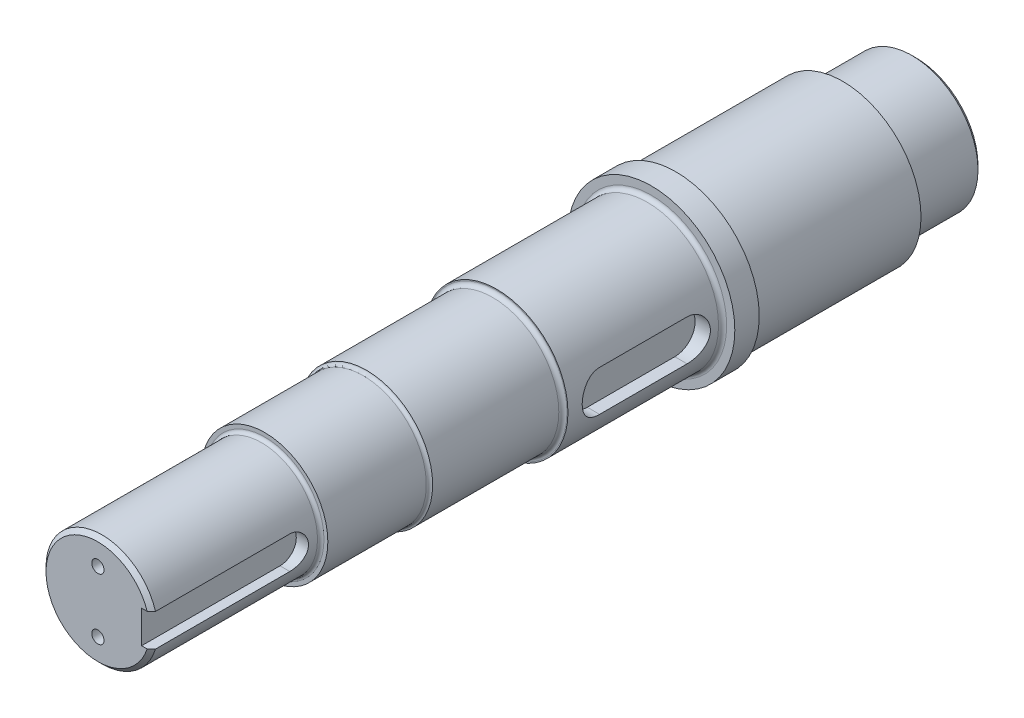
SolidWorks part; units mm, degrees
ref_plane "前视基准面" through (0, 0, 0) normal (0, 0, 1) x (1, 0, 0)
ref_plane "上视基准面" through (0, 0, 0) normal (0, 1, 0) x (1, 0, 0)
ref_plane "右视基准面" through (0, 0, 0) normal (1, 0, 0) x (0, 0, -1)
sketch "草图1" plane through (0, 0, 0) normal (0, 0, 1) x (1, 0, 0)
  circle A0 centre (0, 0) radius 32.5
  dimension "D1" = 65
extrude "凸台-拉伸1" add sketch "草图1" along normal blind 36
sketch "草图2" plane through (0, 0, 36) normal (0, 0, 1) x (1, 0, 0)
  circle A0 centre (0, 0) radius 38.5
  dimension "D1" = 77
extrude "凸台-拉伸2" add sketch "草图2" along normal blind 82
sketch "草图3" plane through (0, 0, 118) normal (0, 0, 1) x (1, 0, 0)
  circle A0 centre (0, 0) radius 41
  dimension "D1" = 82
extrude "凸台-拉伸3" add sketch "草图3" along normal blind 12
sketch "草图4" plane through (0, 0, 130) normal (0, 0, 1) x (1, 0, 0)
  circle A0 centre (0, 0) radius 35
  dimension "D1" = 70
extrude "凸台-拉伸4" add sketch "草图4" along normal blind 76
sketch "草图5" plane through (0, 0, 206) normal (0, 0, 1) x (1, 0, 0)
  circle A0 centre (0, 0) radius 32.5
  dimension "D1" = 65
extrude "凸台-拉伸5" add sketch "草图5" along normal blind 64
sketch "草图6" plane through (0, 0, 270) normal (0, 0, 1) x (1, 0, 0)
  circle A0 centre (0, 0) radius 31
  dimension "D1" = 62
extrude "凸台-拉伸6" add sketch "草图6" along normal blind 50
sketch "草图7" plane through (0, 0, 320) normal (0, 0, 1) x (1, 0, 0)
  circle A0 centre (0, 0) radius 27.5
  dimension "D1" = 55
extrude "凸台-拉伸7" add sketch "草图7" along normal blind 82
fillet "圆角1" radius 2 2 edges at (32.5, 0, 206) (35, 0, 130)
fillet "圆角2" radius 1.6 2 edges at (27.5, 0, 320) (31, 0, 270)
chamfer "倒角1" distance 2 angle 45 2 edges at (32.5, 0, 0) (27.5, 0, 402)
ref_plane "基准面1" through (27.5, 0, 0) normal (1, 0, 0) x (0, 0, -1)
sketch "草图8" plane through (27.5, 0, 0) normal (1, 0, 0) x (0, 0, -1)
  line L0 (-202.5, 0) -> (-135.849, 0) construction
  line L1 (-130, 37) -> (-130, -37) construction
  line L2 (-189, 10) -> (-146, 10)
  line L4 (-189, -10) -> (-146, -10)
  arc A0 (-146, -10) -> (-146, 10) centre (-146, 0) ccw
  arc A1 (-189, 10) -> (-189, -10) centre (-189, 0) ccw
  dimension "D4" = 20
  dimension "D5" = 20
  dimension "D1" = 20
  dimension "D2" = 10
  dimension "D3" = 43
  dimension "D6" = 16
extrude "切除-拉伸1" cut sketch "草图8" along normal blind 29
ref_plane "基准面2" through (21.5, 0, 0) normal (1, 0, 0) x (0, 0, -1)
sketch "草图9" plane through (21.5, 0, 0) normal (1, 0, 0) x (0, 0, -1)
  line L0 (-409.335, 0) -> (-328.903, 0) construction
  line L1 (-402, 25.5) -> (-402, -25.5) construction
  line L2 (-402, 8) -> (-334, 8)
  line L3 (-402, 8) -> (-402, -8)
  line L4 (-402, -8) -> (-334, -8)
  arc A0 (-334, -8) -> (-334, 8) centre (-334, 0) ccw
  dimension "D1" = 8
  dimension "D2" = 16
  dimension "D3" = 68
extrude "切除-拉伸2" cut sketch "草图9" along normal blind 20
sketch "草图10" plane through (0, 0, 402) normal (0, 0, 1) x (1, 0, 0)
  line L0 (0, 18.073) -> (0, -20.554) construction
  line L1 (-19.49, 0) -> (17.896, 0) construction
  circle A0 centre (0, 15) radius 3
  circle A1 centre (0, -15) radius 3
  dimension "D1" = 6
  dimension "D2" = 15
extrude "切除-拉伸3" cut sketch "草图10" against normal blind 20
